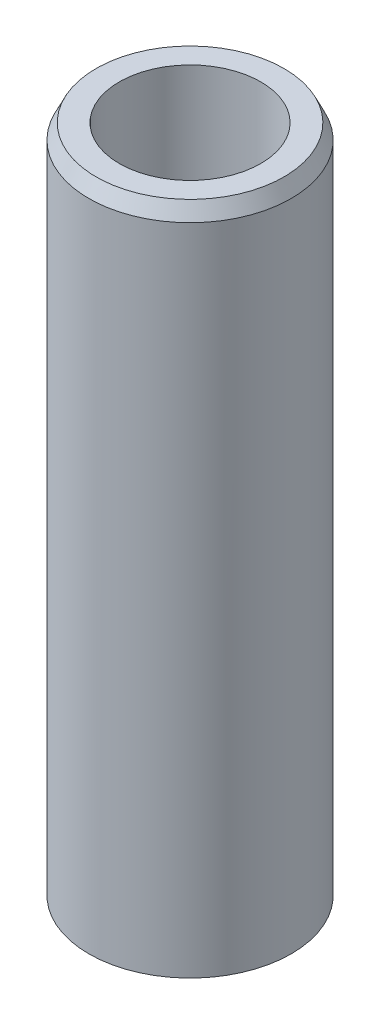
SolidWorks part; units mm, degrees
ref_plane "Front Plane" through (0, 0, 0) normal (0, 0, 1) x (1, 0, 0)
ref_plane "Top Plane" through (0, 0, 0) normal (0, 1, 0) x (1, 0, 0)
ref_plane "Right Plane" through (0, 0, 0) normal (1, 0, 0) x (0, 0, -1)
sketch "Sketch1" plane through (0, 0, 0) normal (0, 1, 0) x (1, 0, 0)
  circle A0 centre (0, 0) radius 25
  dimension "SHAFT_OD" = 50
extrude "Boss-Extrude1" add sketch "Sketch1" along normal blind 167.1157
sketch "Sketch2" plane through (0, 0, 0) normal (0, 1, 0) x (1, 0, 0)
  circle A0 centre (0, 0) radius 17.4832
  dimension "BORE_D" = 34.9664
extrude "Cut-Extrude1" cut sketch "Sketch2" along normal through all
chamfer "Chamfer1" distance 3.722 angle 25.727 2 edges at (0, 167.1157, 25) (0, 0, 25) first distance on face at (0, 167.1157, 25) first distance on face at (0, 0, 17.4832)
